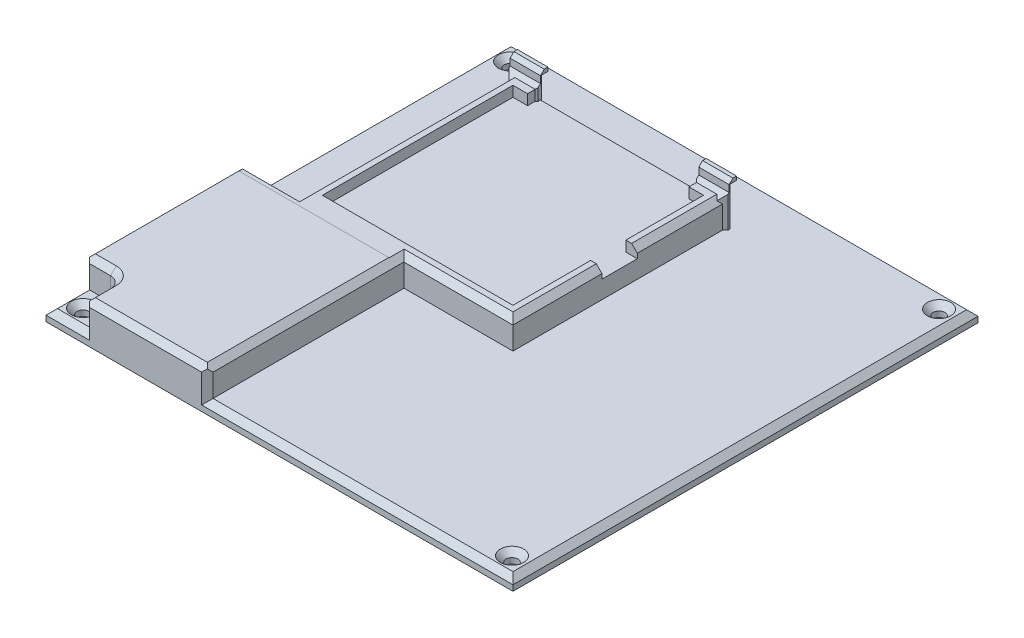
SolidWorks part; units mm, degrees
note: The reader was unsure of these and kept them because the rebuilt part matched: shared geometry of "Sketch2<3>".
ref_plane "Front Plane" through (0, 0, 0) normal (0, 0, 1) x (1, 0, 0)
ref_plane "Top Plane" through (0, 0, 0) normal (0, 1, 0) x (1, 0, 0)
ref_plane "Right Plane" through (0, 0, 0) normal (1, 0, 0) x (0, 0, -1)
sketch "Sketch1" plane through (0, 0, 0) normal (0, 1, 0) x (1, 0, 0)
  line L0 (-6, -6) -> (-6, 106.4)
  line L1 (0, 0) -> (100.4, 0)
  line L2 (0, 0) -> (0, 100.4)
  line L3 (0, 100.4) -> (7.7, 100.4)
  line L4 (100.4, 0) -> (100.4, 40.9)
  line L5 (-6, 106.4) -> (7.7, 106.4)
  line L6 (106.4, -6) -> (106.4, 40.9)
  line L7 (-6, -6) -> (106.4, -6)
  line L8 (100.4, 0) -> (100.4, 100.4) construction
  line L9 (50.2, 100.4) -> (50.2, 0) construction
  line L10 (100.4, 50.2) -> (0, 50.2) construction
  line L11 (92.7, 100.4) -> (92.7, 106.4)
  line L12 (7.7, 100.4) -> (7.7, 106.4)
  line L13 (92.7, 100.4) -> (100.4, 100.4)
  line L14 (0, 100.4) -> (100.4, 100.4) construction
  line L15 (92.7, 106.4) -> (106.4, 106.4)
  line L16 (-6, 106.4) -> (106.4, 106.4) construction
  line L17 (100.4, 59.5) -> (106.4, 59.5)
  line L18 (100.4, 40.9) -> (106.4, 40.9)
  line L19 (100.4, 59.5) -> (100.4, 100.4)
  line L20 (106.4, 59.5) -> (106.4, 106.4)
  line L21 (106.4, -6) -> (106.4, 106.4) construction
  dimension "D1" = 100.4
  dimension "D2" = 100.4
  dimension "D4" = 85
  dimension "D5" = 42.5
  dimension "D6" = 18.6
  dimension "D7" = 9.3
  dimension "D3" = 6
extrude "Boss-Extrude1" add sketch "Sketch1" along normal blind 5.5
sketch "Sketch2" plane through (0, 0, 0) normal (0, -1, 0) x (1, 0, 0)
  line L0 (0, -100.4) -> (7.7, -100.4) construction
  line L1 (-36, 109.6) -> (210, 109.6)
  line L2 (-36, 109.6) -> (-36, -135.4)
  line L3 (-36, -135.4) -> (210, -135.4)
  line L4 (210, 109.6) -> (210, -135.4)
  line L5 (0, 0) -> (0, -100.4) construction
  line L6 (106.4, -106.4) -> (92.7, -106.4) construction
  line L7 (-6, 6) -> (106.4, 6)
  line L8 (-6, 6) -> (-6, -106.4)
  line L9 (-6, -106.4) -> (106.4, -106.4)
  line L10 (106.4, 6) -> (106.4, -106.4)
  dimension "D1" = 246
  dimension "D2" = 245
  dimension "D3" = 210
  dimension "D4" = 210
extrude "Boss-Extrude2" add sketch "Sketch2" along normal blind 9.4 contours L10 L9 L8 L7
extrude "Boss-Extrude3" add sketch "Sketch2<3>" along normal blind 6 from surface at 9.4 contours L2 L3 L4 L1 starting at face at (50.2, -9.4, -50.2)
sketch "Sketch2<3>" plane through (0, 0, 0) normal (0, -1, 0) x (1, 0, 0) same geometry as "Sketch2"
sketch "Sketch3" plane through (0, -9.4, 0) normal (0, 1, 0) x (1, 0, 0)
  line L0 (-36, 135.4) -> (210, 135.4) construction
  line L1 (87, 135.4) -> (87, -109.6) construction
  line L2 (-36, -109.6) -> (210, -109.6) construction
  line L3 (210, 12.9) -> (-36, 12.9) construction
  line L4 (210, -109.6) -> (210, 135.4) construction
  line L5 (-36, -109.6) -> (-36, 135.4) construction
  circle A0 centre (-26.5, 125.4) radius 3.1
  circle A3 centre (-26.5, -99.6) radius 3.1
  circle A4 centre (199.5, 125.4) radius 3.1
  circle A5 centre (199.5, -99.6) radius 3.1
  dimension "D1" = 6.2
  dimension "D5" = 112.5
  dimension "D7" = 112.5
  dimension "D2" = 113.5
  dimension "D3" = 112.5
  dimension "D4" = 112.5
  dimension "D6" = 112.5
extrude "Cut-Extrude1" cut sketch "Sketch3" against normal through all
sketch "Sketch4" plane through (0, -9.4, 0) normal (0, 1, 0) x (1, 0, 0)
  line L0 (-6, -6) -> (106.4, -6) construction
  line L1 (-16, -109.6) -> (49, -109.6)
  line L2 (-36, -89.6) -> (-36, -6)
  line L3 (-36, -6) -> (49, -6)
  line L4 (49, -109.6) -> (49, -6)
  line L5 (-36, -109.6) -> (210, -109.6) construction
  line L8 (-36, -89.6) -> (-22, -89.6)
  line L9 (-16, -109.6) -> (-16, -95.6)
  line L10 (-36, -109.6) -> (-36, 135.4) construction
  arc A0 (-22, -89.6) -> (-16, -95.6) centre (-22, -95.6) cw
  point P15 (-16, -89.6)
  dimension "D4" = 6
  dimension "D1" = 85
  dimension "D2" = 20
  dimension "D3" = 20
extrude "Boss-Extrude4" add sketch "Sketch4" along normal blind 15
sketch "Sketch5" plane through (0, 0, -106.4) normal (0, 0, -1) x (-1, 0, 0)
  line L0 (-107.9, -9.4) -> (-107.9, 13.1)
  line L1 (-8.5, -9.4) -> (7.5, -9.4)
  line L2 (-8.5, -9.4) -> (-8.5, 13.1)
  line L3 (-8.5, 13.1) -> (7.5, 13.1)
  line L4 (7.5, -9.4) -> (7.5, 13.1)
  line L5 (36, -9.4) -> (-210, -9.4) construction
  line L6 (6, 5.5) -> (6, -9.4) construction
  line L7 (-91.9, 13.1) -> (-107.9, 13.1)
  line L8 (-50.2, 0) -> (-50.2, -9.4) construction
  line L9 (-7.7, 0) -> (-92.7, 0) construction
  line L10 (6, -9.4) -> (-106.4, -9.4) construction
  line L11 (-91.9, -9.4) -> (-91.9, 13.1)
  line L12 (-91.9, -9.4) -> (-107.9, -9.4)
  dimension "D1" = 16
  dimension "D2" = 22.5
  dimension "D3" = 14.5
extrude "Boss-Extrude5" add sketch "Sketch5" along normal blind 3.9
sketch "Sketch6" plane through (0, 0, -110.3) normal (0, 0, -1) x (-1, 0, 0)
  line L0 (-8.5, 13.1) -> (-8.5, -9.4) construction
  line L1 (-8.5, 11.1) -> (7.5, 11.1)
  line L2 (-8.5, 11.1) -> (-8.5, -9.4)
  line L3 (-8.5, -9.4) -> (7.5, -9.4)
  line L4 (7.5, 11.1) -> (7.5, -9.4)
  line L5 (7.5, 13.1) -> (-8.5, 13.1) construction
  line L6 (-50.2, 0) -> (-50.2, -9.4) construction
  line L7 (-8.5, 0) -> (-91.9, 0) construction
  line L8 (-8.5, -9.4) -> (-91.9, -9.4) construction
  line L9 (-107.9, 11.1) -> (-107.9, -9.4)
  line L10 (-91.9, -9.4) -> (-107.9, -9.4)
  line L11 (-91.9, 11.1) -> (-91.9, -9.4)
  line L12 (-91.9, 11.1) -> (-107.9, 11.1)
  dimension "D1" = 2
extrude "Cut-Extrude2" cut sketch "Sketch6" against normal blind 3.4
chamfer "Chamfer1" distance 2 angle 45 8 edges at (99.9, 13.1, -106.4) (92.7, 2.75, -106.4) (99.55, 5.5, -106.4) (106.4, -1.95, -106.4) (0.5, 13.1, -106.4) (7.7, 2.75, -106.4) (0.85, 5.5, -106.4) (-6, -1.95, -106.4)
chamfer "Chamfer2" distance 3.05 angle 45 4 edges at (199.5, -9.4, -122.3) (-26.5, -9.4, -122.3) (-26.5, -9.4, 96.5) (199.5, -9.4, 102.7)
chamfer "Chamfer3" distance 3 angle 45 11 edges at (106.4, 5.5, -81.95) (-6, 5.5, -49.2) (6.5, 5.6, 6) (-36, 5.6, 47.8) (-29, 5.6, 89.6) (-16, 5.6, 102.6) (-17.7574, 5.6, 91.3574) (106.4, 5.5, -17.45) (77.7, 5.5, 6) (49, 5.6, 57.8) (16.5, 5.6, 109.6)
chamfer "Chamfer4" distance 3 angle 45 11 edges at (-36, -9.4, -64.7) (129.5, -9.4, 109.6) (-36, -3.4, 89.6) (-36, -3.4, 6) (-34.5, 4.1, 6) (-16, -3.4, 109.6) (49, -3.4, 109.6) (-36, -9.4, 99.6) (87, -9.4, -135.4) (-26, -9.4, 109.6) (210, -9.4, -12.9)
sketch "Sketch8" plane through (0, 5.6, 0) normal (0, 1, 0) x (1, 0, 0)
  line L0 (-33, -6) -> (-33, -86.6) construction
  line L1 (46.1, -6) -> (-33, -6)
  line L2 (46.1, -6) -> (46.1, -11)
  line L3 (46.1, -11) -> (-33, -11)
  line L4 (-33, -6) -> (-33, -11)
  dimension "D1" = 5
extrude "Cut-Extrude3" cut sketch "Sketch8" against normal blind 0.1
chamfer "Chamfer5" distance 3 angle 45 1 edges at (-18, 5.5, 6)
